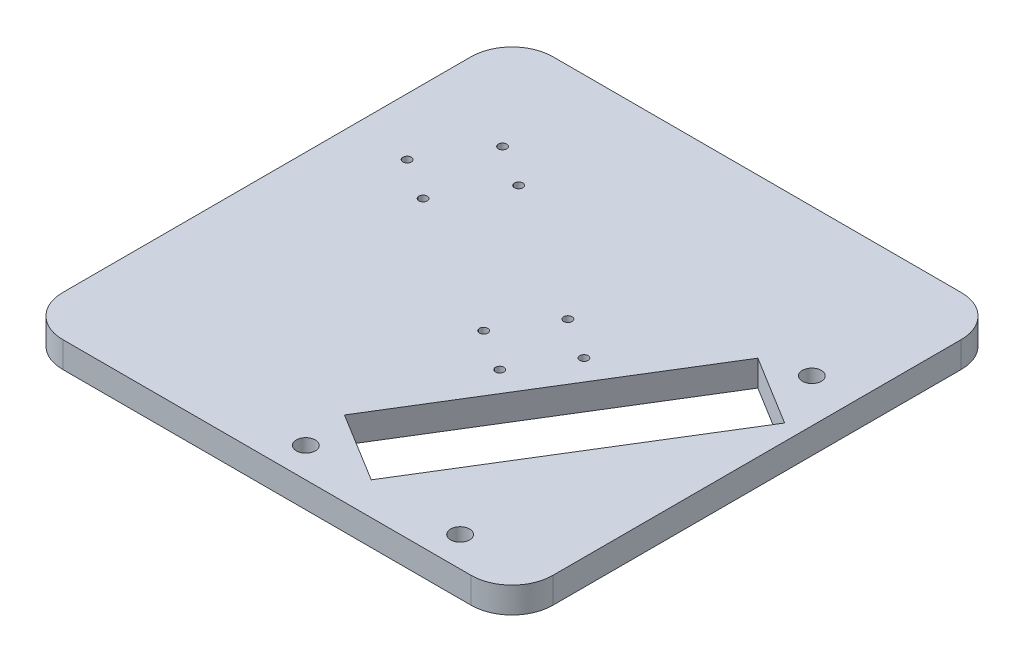
SolidWorks part; units mm, degrees
material "Beech"
ref_plane "Front Plane" through (0, 0, 0) normal (0, 0, 1) x (1, 0, 0)
ref_plane "Top Plane" through (0, 0, 0) normal (0, 1, 0) x (1, 0, 0)
ref_plane "Right Plane" through (0, 0, 0) normal (1, 0, 0) x (0, 0, -1)
sketch "Sketch1" plane through (0, 0, 0) normal (0, 1, 0) x (1, 0, 0)
  line L1 (10, 0) -> (110, 0)
  line L2 (0, 10) -> (0, 110)
  line L3 (10, 120) -> (110, 120)
  line L4 (120, 10) -> (120, 110)
  arc A0 (110, 0) -> (120, 10) centre (110, 10) ccw
  arc A1 (10, 0) -> (0, 10) centre (10, 10) cw
  arc A2 (0, 110) -> (10, 120) centre (10, 110) cw
  arc A3 (110, 120) -> (120, 110) centre (110, 110) cw
  point P7 (120, 0)
  point P10 (0, 0)
  point P13 (0, 120)
  point P16 (120, 120)
  dimension "D3" = 10
  dimension "D1" = 120
  dimension "D2" = 120
extrude "Boss-Extrude1" add sketch "Sketch1" along normal blind 6.35
sketch "Sketch2" plane through (0, 6.35, 0) normal (0, 1, 0) x (1, 0, 0)
  line L0 (58.0317, 5) -> (102.0317, 5) construction
  line L1 (102.0317, 5) -> (113, 94.33) construction
  line L2 (113, 94.33) -> (58.0317, 5) construction
  line L5 (60.4717, 18.5061) -> (77.5052, 8.0247)
  line L6 (77.5052, 8.0247) -> (116.0663, 70.6909)
  line L7 (116.0663, 70.6909) -> (99.0328, 81.1723)
  line L8 (60.4717, 18.5061) -> (99.0328, 81.1723)
  line L9 (10, 0) -> (110, 0) construction
  line L10 (120, 10) -> (120, 110) construction
  circle A0 centre (62.1922, 7.325) radius 2.325
  circle A1 centre (99.9747, 7.325) radius 2.325
  circle A2 centre (109.3931, 84.0319) radius 2.325
  dimension "D6" = 4.65
  dimension "D7" = 4.65
  dimension "D8" = 4.65
  dimension "D1" = 97
  dimension "D2" = 44
  dimension "D3" = 89.33
  dimension "D4" = 5
  dimension "D5" = 7
  dimension "D9" = 20
  dimension "D10" = 73.58
  dimension "D11" = 5
  dimension "D12" = 7.865
  dimension "D13" = 8.6209
extrude "Cut-Extrude1" cut sketch "Sketch2" against normal through all
sketch "Sketch5" plane through (0, 6.35, 0) normal (0, 1, 0) x (1, 0, 0)
  line L0 (79.7522, 49.8392) -> (0, 98.9139) construction
  line L1 (99.0328, 81.1723) -> (60.4717, 18.5061) construction
  line L2 (0, 110) -> (0, 10) construction
  circle A0 centre (69.86, 47.1201) radius 1.025
  circle A1 centre (59.6399, 53.409) radius 1.025
  circle A2 centre (77.721, 59.8952) radius 1.025
  circle A3 centre (67.5009, 66.1841) radius 1.025
  circle A4 centre (13.977, 80.333) radius 1.025
  circle A5 centre (24.1971, 74.0441) radius 1.025
  circle A6 centre (33.1063, 88.5226) radius 1.025
  circle A7 centre (22.8862, 94.8115) radius 1.025
  dimension "D2" = 2.05
  dimension "D3" = 2.05
  dimension "D4" = 2.05
  dimension "D5" = 2.05
  dimension "D14" = 2.05
  dimension "D15" = 2.05
  dimension "D16" = 2.05
  dimension "D17" = 2.05
  dimension "D1" = 90
  dimension "D6" = 7.5
  dimension "D7" = 7.5
  dimension "D8" = 7.5
  dimension "D9" = 7.5
  dimension "D10" = 7
  dimension "D11" = 7
  dimension "D12" = 12
  dimension "D13" = 12
  dimension "D18" = 8.5
  dimension "D19" = 8.5
  dimension "D20" = 8.5
  dimension "D21" = 8.5
  dimension "D22" = 60
  dimension "D23" = 60
  dimension "D24" = 12
  dimension "D25" = 12
extrude "Cut-Extrude2" cut sketch "Sketch5" against normal through all
sketch "Sketch4" plane through (0, 0, 0) normal (0, -1, 0) x (1, 0, 0)
  line L0 (79.7522, -49.8392) -> (96.7857, -39.3578) construction
  line L1 (99.0328, -81.1723) -> (60.4717, -18.5061) construction
  line L2 (77.5052, -8.0247) -> (116.0663, -70.6909) construction
sketch "Sketch6" plane through (0, 6.35, 0) normal (0, 1, 0) x (1, 0, 0)
  line L0 (79.7522, 49.8392) -> (96.7857, 39.3578) construction
